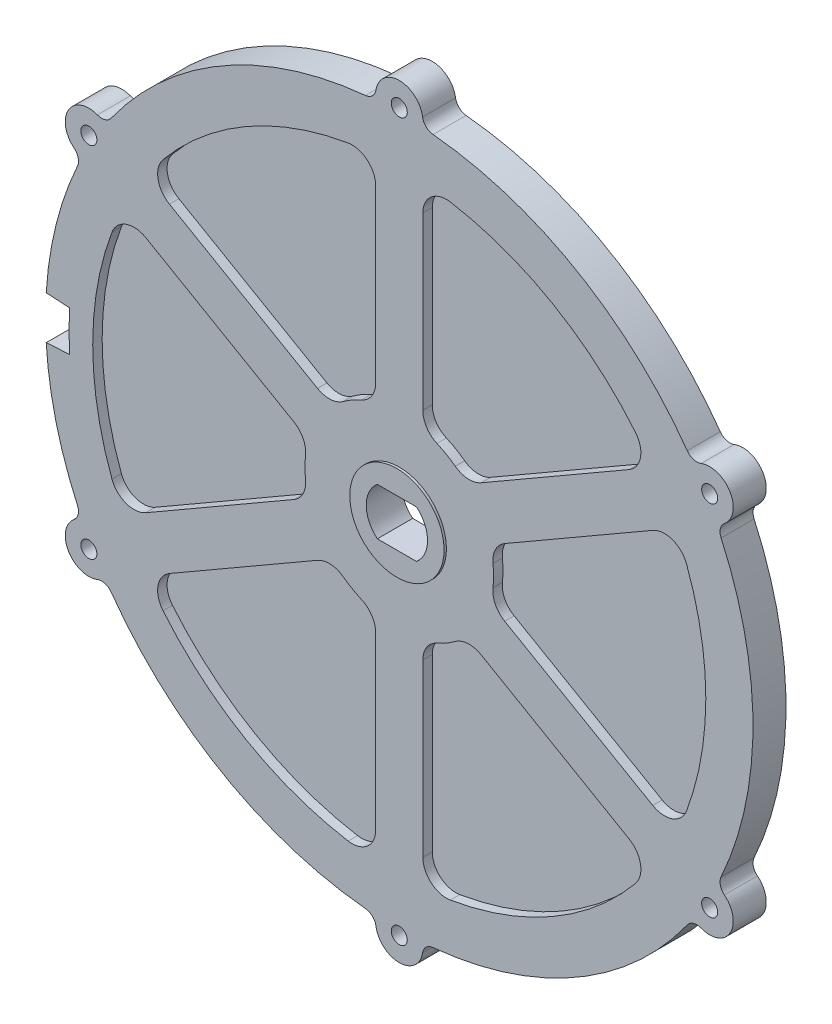
SolidWorks part; units mm, degrees
ref_plane "Front Plane" through (0, 0, 0) normal (0, 0, 1) x (1, 0, 0)
ref_plane "Top Plane" through (0, 0, 0) normal (0, 1, 0) x (1, 0, 0)
ref_plane "Right Plane" through (0, 0, 0) normal (1, 0, 0) x (0, 0, -1)
sketch "Sketch2" plane through (0, 0, 0) normal (0, 0, 1) x (1, 0, 0)
  line L0 (4.1533, 5) -> (-4.1533, 5)
  line L1 (4.1533, -5) -> (-4.1533, -5)
  circle A0 centre (0, 0) radius 75
  circle A1 centre (0, 0) radius 6.5
  dimension "D1" = 150
  dimension "D2" = 13
  dimension "D3" = 10
extrude "Boss-Extrude1" add sketch "Sketch2" along normal mid plane 7 contours A0 A1 | L0 A1 | L1 A1 region at (0, 5.6064, 0) region at (0, -5.6064, 0) region at (-72.8787, 0, 0)
sketch "Sketch3" plane through (0, 0, 3.5) normal (0, 0, 1) x (1, 0, 0)
  circle A0 centre (0, 0) radius 10
  arc M2 (4.1533, 5) -> (4.1533, -5) centre (0, 0) cw
  line M3 (4.1533, -5) -> (-4.1533, -5)
  arc M4 (-4.1533, -5) -> (-4.1533, 5) centre (0, 0) cw
  line M5 (-4.1533, 5) -> (4.1533, 5)
  dimension "D1" = 20
extrude "Boss-Extrude2" add sketch "Sketch3" along normal blind 0.5 contours A0 M5 M2 M3 M4 region at (-9.7172, 0, 3.5)
sketch "Sketch4" plane through (0, 0, -3.5) normal (0, 0, 1) x (1, 0, 0)
  line L0 (5, 76) -> (5, 74.8331)
  line L1 (-5, 76) -> (-5, 74.8331)
  arc A0 (5, 76) -> (-5, 76) centre (0, 76) ccw
  circle A1 centre (0, 0) radius 75 construction
  circle A3 centre (0, 0) radius 75
  arc A4 (-5, 74.8331) -> (5, 74.8331) centre (0, 0) ccw
  circle M9 centre (0, 0) radius 75
  dimension "D1" = 5
  dimension "D2" = 76
  dimension "D3" = 0
extrude "Boss-Extrude3" add sketch "Sketch4" along normal up to surface (7 mm away) contours A0 L0 L1 M9 region at (0, 77.5604, -3.5) up to face at (10, 0, 3.5)
fillet "Fillet1" radius 2.5 2 edges at (-5, 74.8331, 0) (5, 74.8331, 0)
sketch "Sketch6" plane through (0, 0, -3.5) normal (0, 0, -1) x (-1, 0, 0)
  circle A0 centre (0, 76) radius 1.7
  arc A4 (4.9414, 76.7632) -> (-4.9414, 76.7632) centre (0, 76) ccw construction
  dimension "D1" = 3.4
extrude "Cut-Extrude1" cut sketch "Sketch6" against normal through all
pattern_circular "CirPattern1" count 6 over 360 about axis through (0, 0, -3.5) along (0, 0, 1) of "Boss-Extrude3", "Cut-Extrude1", "Fillet1"
sketch "Sketch7" plane through (0, 0, -3.5) normal (0, 0, -1) x (-1, 0, 0)
  line L0 (-5, 59.1608) -> (-5, 22.9129)
  line L1 (5, 59.1608) -> (5, 22.9129)
  line L2 (-5, 19.3649) -> (5, 19.3649) construction
  line L3 (48.7348, 33.9105) -> (17.3431, 15.7866)
  line L4 (53.7348, 25.2503) -> (22.3431, 7.1263)
  line L6 (53.7348, -25.2503) -> (22.3431, -7.1263)
  line L7 (48.7348, -33.9105) -> (17.3431, -15.7866)
  line L9 (5, -59.1608) -> (5, -22.9129)
  line L10 (-5, -59.1608) -> (-5, -22.9129)
  line L12 (-48.7348, -33.9105) -> (-17.3431, -15.7866)
  line L13 (-53.7348, -25.2503) -> (-22.3431, -7.1263)
  line L15 (-53.7348, 25.2503) -> (-22.3431, 7.1263)
  line L16 (-48.7348, 33.9105) -> (-17.3431, 15.7866)
  line L18 (0, 0) -> (8, 18.3303) construction
  line L19 (14.2705, 14.0126) -> (19.2705, 5.3523) construction
  line L20 (19.2705, -5.3523) -> (14.2705, -14.0126) construction
  line L21 (5, -19.3649) -> (-5, -19.3649) construction
  line L22 (-14.2705, -14.0126) -> (-19.2705, -5.3523) construction
  line L23 (-19.2705, 5.3523) -> (-14.2705, 14.0126) construction
  arc A0 (-8, 18.3303) -> (-11.8745, 16.0934) centre (0, 0) ccw
  arc A1 (-10.8333, 64.0909) -> (-50.0876, 41.4274) centre (0, 0) ccw
  arc A2 (5, 22.9129) -> (8, 18.3303) centre (10, 22.9129) ccw
  arc A3 (5, 59.1608) -> (10.8333, 64.0909) centre (10, 59.1608) cw
  arc A4 (-5, 59.1608) -> (-10.8333, 64.0909) centre (-10, 59.1608) ccw
  arc A5 (-5, 22.9129) -> (-8, 18.3303) centre (-10, 22.9129) cw
  arc A6 (22.3431, 7.1263) -> (19.8745, 2.2369) centre (24.8431, 2.7962) ccw
  arc A7 (53.7348, 25.2503) -> (60.921, 22.6635) centre (56.2348, 20.9201) cw
  arc A8 (48.7348, 33.9105) -> (50.0876, 41.4274) centre (46.2348, 38.2407) ccw
  arc A9 (17.3431, 15.7866) -> (11.8745, 16.0934) centre (14.8431, 20.1167) cw
  arc A10 (17.3431, -15.7866) -> (11.8745, -16.0934) centre (14.8431, -20.1167) ccw
  arc A11 (48.7348, -33.9105) -> (50.0876, -41.4274) centre (46.2348, -38.2407) cw
  arc A12 (53.7348, -25.2503) -> (60.921, -22.6635) centre (56.2348, -20.9201) ccw
  arc A13 (22.3431, -7.1263) -> (19.8745, -2.2369) centre (24.8431, -2.7962) cw
  arc A14 (-5, -22.9129) -> (-8, -18.3303) centre (-10, -22.9129) ccw
  arc A15 (-5, -59.1608) -> (-10.8333, -64.0909) centre (-10, -59.1608) cw
  arc A16 (5, -59.1608) -> (10.8333, -64.0909) centre (10, -59.1608) ccw
  arc A17 (5, -22.9129) -> (8, -18.3303) centre (10, -22.9129) cw
  arc A18 (-22.3431, -7.1263) -> (-19.8745, -2.2369) centre (-24.8431, -2.7962) ccw
  arc A19 (-53.7348, -25.2503) -> (-60.921, -22.6635) centre (-56.2348, -20.9201) cw
  arc A20 (-48.7348, -33.9105) -> (-50.0876, -41.4274) centre (-46.2348, -38.2407) ccw
  arc A21 (-17.3431, -15.7866) -> (-11.8745, -16.0934) centre (-14.8431, -20.1167) cw
  arc A22 (-17.3431, 15.7866) -> (-11.8745, 16.0934) centre (-14.8431, 20.1167) ccw
  arc A23 (-48.7348, 33.9105) -> (-50.0876, 41.4274) centre (-46.2348, 38.2407) cw
  arc A24 (-53.7348, 25.2503) -> (-60.921, 22.6635) centre (-56.2348, 20.9201) ccw
  arc A25 (-22.3431, 7.1263) -> (-19.8745, 2.2369) centre (-24.8431, 2.7962) cw
  arc A26 (11.8745, 16.0934) -> (8, 18.3303) centre (0, 0) ccw
  arc A27 (19.8745, -2.2369) -> (19.8745, 2.2369) centre (0, 0) ccw
  arc A28 (8, -18.3303) -> (11.8745, -16.0934) centre (0, 0) ccw
  arc A29 (-11.8745, -16.0934) -> (-8, -18.3303) centre (0, 0) ccw
  arc A30 (-19.8745, 2.2369) -> (-19.8745, -2.2369) centre (0, 0) ccw
  arc A31 (50.0876, 41.4274) -> (10.8333, 64.0909) centre (0, 0) ccw
  arc A32 (60.921, -22.6635) -> (60.921, 22.6635) centre (0, 0) ccw
  arc A33 (10.8333, -64.0909) -> (50.0876, -41.4274) centre (0, 0) ccw
  arc A34 (-50.0876, -41.4274) -> (-10.8333, -64.0909) centre (0, 0) ccw
  arc A35 (-60.921, 22.6635) -> (-60.921, -22.6635) centre (0, 0) ccw
  point P8 (0, 19.3649)
  dimension "D1" = 130
  dimension "D2" = 40
  dimension "D4" = 5
  dimension "D3" = 10
  dimension "D5" = 6
extrude "Cut-Extrude2" cut sketch "Sketch7" against normal blind 2
mirror "Mirror1" about plane through (0, 0, 0) normal (0, 0, 1) of "Cut-Extrude2"
sketch "Sketch9" plane through (0, 0, 0) normal (0, 1, 0) x (1, 0, 0)
  line L0 (-7.173, 3.5) -> (-61.0677, 3.5) construction
  line L1 (-75, -3.5) -> (-70, -3.5)
  line L2 (-75, -3.5) -> (-75, 3.5)
  line L3 (-75, 3.5) -> (-70, 3.5)
  line L4 (-70, -3.5) -> (-70, 3.5)
  line L5 (-61.0677, -3.5) -> (-7.173, -3.5) construction
  line L6 (0, 0) -> (0, 49.8627) construction
  line L7 (-68.2407, 3.5) -> (-75, 3.5) construction
  line L8 (-75, 3.5) -> (-75, -3.5) construction
  point P13 (0, 0)
  dimension "D1" = 5
revolve "Cut-Revolve1" cut sketch "Sketch9" angle 7 mid plane about L6
